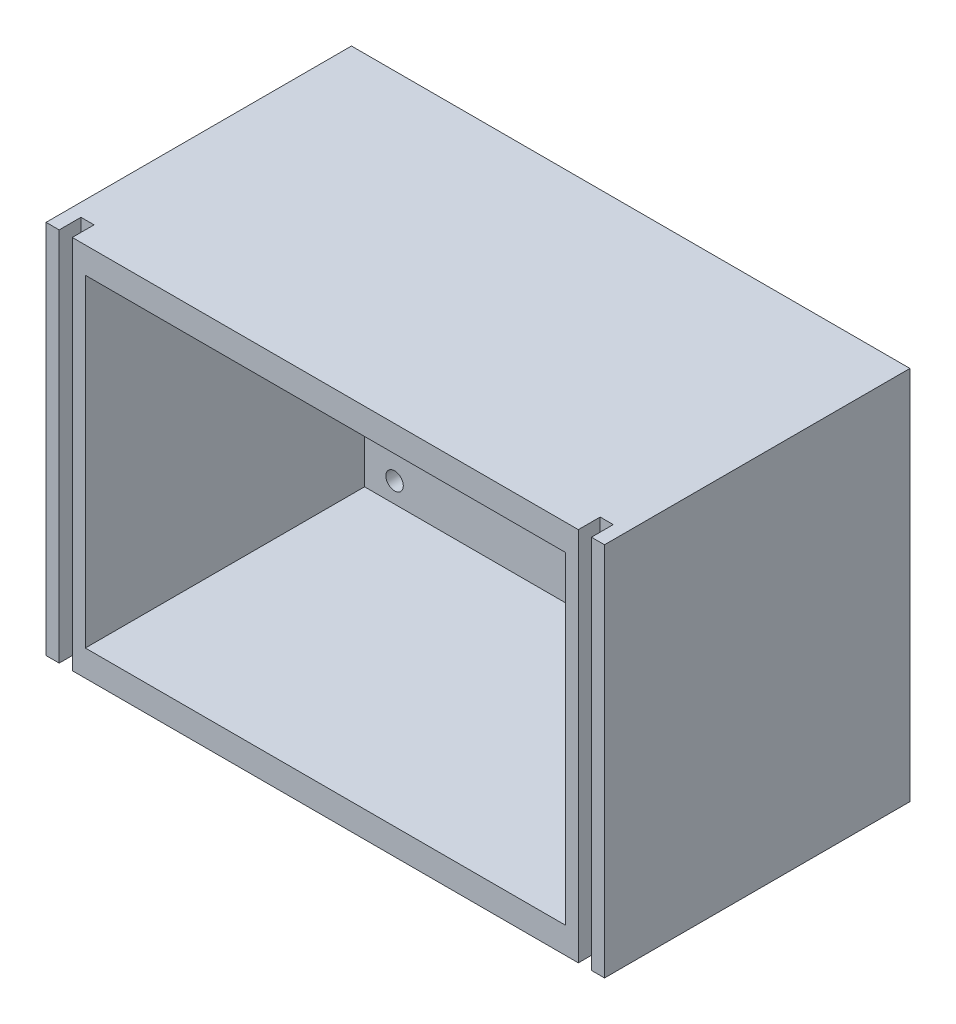
SolidWorks part; units mm, degrees
ref_plane "Спереди" through (0, 0, 0) normal (0, 0, 1) x (1, 0, 0)
ref_plane "Сверху" through (0, 0, 0) normal (0, 1, 0) x (1, 0, 0)
ref_plane "Справа" through (0, 0, 0) normal (1, 0, 0) x (0, 0, -1)
sketch "Эскиз1" plane through (0, 0, 0) normal (0, 0, 1) x (1, 0, 0)
  line L0 (-52.5773, 38.2784) -> (57.4227, -35.7216)
  line L1 (-52.5773, 38.2784) -> (57.4227, 38.2784)
  line L2 (-52.5773, 38.2784) -> (-52.5773, -35.7216)
  line L3 (-52.5773, -35.7216) -> (57.4227, -35.7216)
  line L4 (57.4227, 38.2784) -> (57.4227, -35.7216)
  line L5 (-52.5773, -35.7216) -> (57.4227, 38.2784)
  line L6 (-52.5773, 38.2784) -> (-52.5773, -35.7216)
  line L7 (-61.5773, 44.2784) -> (66.4227, 44.2784)
  line L8 (-61.5773, 44.2784) -> (-61.5773, -41.7216)
  line L9 (-61.5773, -41.7216) -> (66.4227, -41.7216)
  line L10 (66.4227, 44.2784) -> (66.4227, -41.7216)
  line L11 (-52.5773, -35.7216) -> (57.4227, -35.7216)
  line L12 (57.4227, -35.7216) -> (57.4227, 38.2784)
  line L13 (57.4227, 38.2784) -> (-52.5773, 38.2784)
  line L14 (-58.5773, 38.2784) -> (-58.5773, 44.2784)
  line L15 (-58.5773, 44.2784) -> (-55.5773, 44.2784)
  line L17 (-55.5773, 38.2784) -> (-55.5773, -35.7216)
  line L19 (-58.5773, -35.7216) -> (-58.5773, 38.2784)
  line L20 (60.4227, -35.7216) -> (60.4227, -41.7216)
  line L23 (63.4227, 38.2784) -> (63.4227, -35.7216)
  line L25 (60.4227, -35.7216) -> (60.4227, 38.2784)
  line L26 (-58.5773, -35.7216) -> (-58.5773, -41.7216)
  line L27 (-55.5773, -35.7216) -> (-55.5773, -41.7216)
  line L28 (-58.5773, -41.7216) -> (-55.5773, -41.7216)
  line L29 (-55.5773, 44.2784) -> (-55.5773, 38.2784)
  line L30 (60.4227, 38.2784) -> (60.4227, 44.2784)
  line L31 (63.4227, 38.2784) -> (63.4227, 44.2784)
  line L32 (63.4227, 44.2784) -> (60.4227, 44.2784)
  line L33 (60.4227, -41.7216) -> (63.4227, -41.7216)
  line L34 (63.4227, -41.7216) -> (63.4227, -35.7216)
  circle A0 centre (-45.7012, 33.6526) radius 2
  circle A1 centre (-45.7012, -31.0959) radius 2
  circle A2 centre (50.5466, 33.6526) radius 2
  circle A3 centre (50.5466, -31.0959) radius 2
  circle A4 centre (-45.7012, 18.6526) radius 2
  circle A5 centre (-45.7012, -16.0959) radius 2
  circle A6 centre (50.5466, -16.0959) radius 2
  circle A7 centre (50.5466, 18.6526) radius 2
  point P8 (2.4227, 1.2784)
  dimension "D3" = 4
  dimension "D6" = 4
  dimension "D7" = 4
  dimension "D9" = 4
  dimension "D18" = 4
  dimension "D20" = 4
  dimension "D22" = 4
  dimension "D24" = 4
  dimension "D1" = 110
  dimension "D2" = 74
  dimension "D4" = 58
  dimension "D5" = 58
  dimension "D8" = 58
  dimension "D10" = 128
  dimension "D11" = 86
  dimension "D12" = 9
  dimension "D13" = 6
  dimension "D14" = 3
  dimension "D15" = 3
  dimension "D16" = 3
  dimension "D17" = 3
  dimension "D19" = 15
  dimension "D21" = 15
  dimension "D23" = 15
  dimension "D25" = 15
extrude "Бобышка-Вытянуть10" add sketch "Эскиз1" along normal blind 70 contours L25 L30 L7 L29 L17 L27 L9 L20 L1 L4 L3 L2 | L34 L9 L10 L7 L31 L23 | L26 L19 L14 L7 L8 L9 region at (-60.0773, 1.2784, 0) region at (2.4227, 42.8343, 0) region at (64.9227, 1.2784, 0)
extrude "Бобышка-Вытянуть11" add sketch "Эскиз1<11>" along normal blind 65 contours L17 L27 L28 L26 L19 L14 L15 L29 | L23 L34 L33 L20 L25 L30 L32 L31
sketch "Эскиз1<11>" plane through (0, 0, 0) normal (0, 0, 1) x (1, 0, 0) same geometry as "Эскиз1"
extrude "Бобышка-Вытянуть12" add sketch "Эскиз1<12>" along normal blind 6 contours A1 L5 L0 A0 L2 | A2 L5 L1 L0 A0 | A3 L0 L5 A1 L3 | A3 L0 L4 L5 A2 region at (2.4227, 25.8928, 0) region at (-34.0248, 1.2784, 0) region at (38.8701, 1.2784, 0) region at (2.4227, -23.336, 0)
sketch "Эскиз1<12>" plane through (0, 0, 0) normal (0, 0, 1) x (1, 0, 0) same geometry as "Эскиз1"
